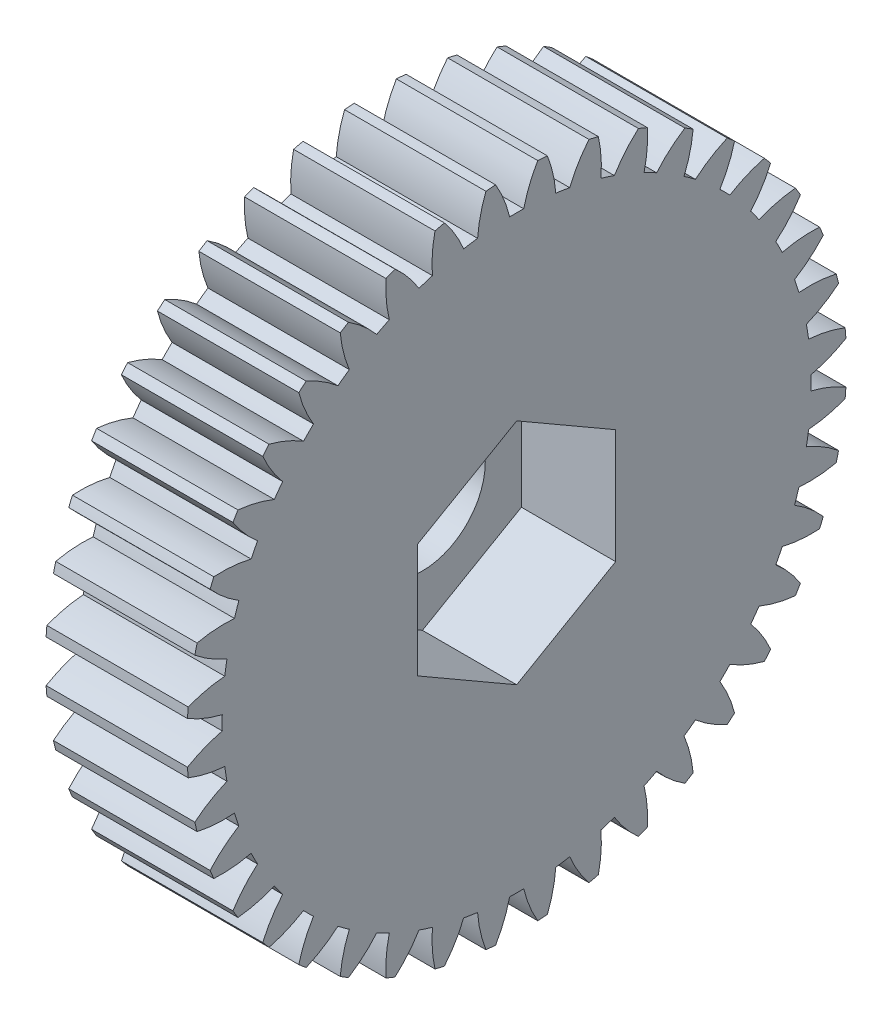
SolidWorks part; units mm, degrees
ref_plane "Plane1" through (0, 0, 0) normal (0, 0, 1) x (1, 0, 0)
ref_plane "Plane2" through (0, 0, 0) normal (0, 1, 0) x (1, 0, 0)
ref_plane "Plane3" through (0, 0, 0) normal (1, 0, 0) x (0, 0, -1)
sketch "HoldingSke" plane through (0, 0, 0) normal (0, 1, 0) x (1, 0, 0)
  line L0 (0, 0) -> (0.766, -0.6428)
  line L1 (-15, 0) -> (100, 0) construction
  line L2 (0, 0) -> (-2.1039, 2.3779)
  line L3 (0, 0) -> (-11.863, 4.5341)
  line L4 (0, 0) -> (6.6156, 5.5511)
  line L5 (0, 0) -> (-46.8476, -17.4728)
  line L6 (0, 0) -> (-7.4607, -5.0337)
  line L7 (-2.1039, 2.3779) -> (8.6586, 51.2059)
  line L8 (-76.2, 54.61) -> (-75.5, 54.61)
  line L9 (-71.009, 38.7566) -> (-53.1078, 45.2721)
  line L10 (-76.2, 71.12) -> (104.1128, 71.12)
  line L11 (0, 0) -> (-9, 0)
  line L12 (-76.2, 101.6) -> (-76.162, 101.6)
  line L13 (24.9733, 27.94) -> (52.9518, 28.4284)
  line L14 (24.9733, 27.94) -> (24.9743, 27.94)
  line L15 (24.9733, 27.94) -> (100.4006, 29.5858)
  line L16 (-63.627, -1) -> (-12.827, -1)
  circle A0 centre (0, 0) radius 2
  circle A1 centre (0, 0) radius 18.749
  circle A2 centre (0, 0) radius 37.5
  circle A3 centre (0, 0) radius 2
  dimension "MHD" = 37.498
  dimension "Hub_dia" = 75
  dimension "Bore" = 4
  dimension "MBD" = 4
  dimension "Num_teeth" = 40
  dimension "Pitch" = 1
  dimension "Overall_len" = 50
  dimension "Show_teeth" = 40
  dimension "Thickness" = 9
  dimension "OAL" = 50.0001
  dimension "T_dim" = 0.7
  dimension "Ap" = 20
  dimension "H" = 19.05
  dimension "Pitch_radius" = 180.3128
  dimension "Width" = 9
  dimension "Backlash" = 0.038
  dimension "Addendum_fac" = 1
  dimension "Dedendum_fac" = 1.25
  dimension "Clearance_fac" = 0.25
  dimension "Dedendum_add" = 0.001
  dimension "Module" = 1
sketch "BasProSke" plane through (0, 0, 0) normal (0, 1, 0) x (1, 0, 0)
  line L0 (-10, 0) -> (60, 0) construction
  line L1 (0, 0) -> (0, 21)
  line L2 (0, 0) -> (9, 0)
  line L3 (9, 0) -> (9, 21)
  line L4 (9, 21) -> (0, 21)
  dimension "Thickness" = 9
  dimension "Diameter" = 42
revolve "Base-Revolve" add sketch "BasProSke" angle 360 about L0
sketch "TooCutSke" plane through (0, 0, 0) normal (1, 0, 0) x (0, 0, -1)
  line L1 (0, 0) -> (0, 107) construction
  line L2 (0, 0) -> (-0.8517, 19.9819) construction
  line L3 (0, 0) -> (-3.1363, 39.8509) construction
  line L4 (-0.8517, 19.9819) -> (-1.5682, 19.9255) construction
  arc A0 (0.4487, 18.7436) -> (-0.4487, 18.7436) centre (0, 0) ccw
  arc A1 (1.3547, 20.9817) -> (-1.3547, 20.9817) centre (0, 0) ccw
  circle A2 centre (0, 0) radius 20 construction
  circle A3 centre (0, 0) radius 18.7939 construction
  arc A4 (-0.4487, 18.7436) -> (-1.3547, 20.9817) centre (-8.2322, 16.895) ccw
  arc A5 (1.3547, 20.9817) -> (0.4487, 18.7436) centre (8.2322, 16.895) ccw
  dimension "Root_dia" = 37.498
  dimension "Overcut_dia" = 42.0508
  dimension "Pitch_dia" = 40
  dimension "Base_dia" = 37.5877
  dimension "Flank_rad" = 8
  dimension "Half_ang" = 4.5
  dimension "Half_CT" = 0.7187
extrude "ToothCut" cut sketch "TooCutSke" along normal through all
fillet "Breaks" [suppressed] radius 0.02 tangent propagation no
fillet "RootFillets" [suppressed] radius 0.251
pattern_circular "TeethCuts" count 40 every 9 about axis through (-10, 0, 0) along (1, 0, 0) of "ToothCut", "RootFillets", "Breaks"
sketch "HubNeaOneSke" plane through (0, 0, 0) normal (-1, 0, 0) x (0, 0, 1)
  circle A0 centre (0, 0) radius 18.749
  dimension "Diameter" = 37.498
extrude "HubNearOne" [suppressed] add sketch "HubNeaOneSke" along normal blind 41.0001
sketch "HubNeaBotSke" plane through (0, 0, 0) normal (-1, 0, 0) x (0, 0, 1)
  circle A0 centre (0, 0) radius 18.749
  dimension "Diameter" = 37.498
extrude "HubNearBoth" [suppressed] add sketch "HubNeaBotSke" along normal blind 20.5
ref_plane "FarPln" through (9, 0, 0) normal (1, 0, 0) x (0, 0, -1)
sketch "HubFarSke" plane through (9, 0, 0) normal (1, 0, 0) x (0, 0, -1)
  circle A0 centre (0, 0) radius 18.749
  dimension "Diameter" = 37.498
extrude "HubFar" [suppressed] add sketch "HubFarSke" along normal blind 20.5
sketch "BorSke" plane through (0, 0, 0) normal (1, 0, 0) x (0, 0, -1)
  circle A0 centre (0, 0) radius 2
extrude "Bore" cut sketch "BorSke" along normal mid plane 100.0001
sketch "KeySke" plane through (0, 0, 0) normal (1, 0, 0) x (0, 0, -1)
  line L0 (-0.8, 0) -> (-0.8, 2.7)
  line L1 (-0.8, 2.7) -> (0.8, 2.7)
  line L2 (0.8, 2.7) -> (0.8, 0)
  line L3 (0, 0) -> (0, 34) construction
  line L4 (-0.8, 0) -> (0.8, 0)
  dimension "Offset" = 2.7
  dimension "Width" = 1.6
extrude "Keyway" [suppressed] cut sketch "KeySke" along normal mid plane 100.0001
pattern_circular "Keyway2" [suppressed] count 2 every 90 about axis through (-10, 0, 0) along (1, 0, 0)
sketch "Sketch1" plane through (9, 0, 0) normal (1, 0, 0) x (0, 0, -1)
  line L1 (0, 7.2746) -> (-6.3, 3.6373)
  line L2 (-6.3, 3.6373) -> (-6.3, -3.6373)
  line L3 (-6.3, -3.6373) -> (0, -7.2746)
  line L4 (0, -7.2746) -> (6.3, -3.6373)
  line L5 (6.3, -3.6373) -> (6.3, 3.6373)
  line L6 (6.3, 3.6373) -> (0, 7.2746)
  circle A0 centre (0, 0) radius 7.2746
  circle A2 centre (0, 0) radius 6.3 construction
  circle A3 centre (0, 0) radius 4
  dimension "D1" = 8
  dimension "D2" = 12.6
extrude "Cut-Extrude1" cut sketch "Sketch1" against normal blind 6 contours L1 L2 L3 L4 L5 L6
extrude "Cut-Extrude2" cut sketch "Sketch1<7>" against normal through all contours A3 region at (9, 0, 0)
sketch "Sketch1<7>" plane through (9, 0, 0) normal (1, 0, 0) x (0, 0, -1) same geometry as "Sketch1"
sketch "Sketch2" plane through (0, 0, 0) normal (-1, 0, 0) x (0, 0, 1)
  circle A0 centre (0, 0) radius 6.5
  circle A1 centre (0, 0) radius 4
  dimension "D1" = 13
  dimension "D2" = 8
extrude "Boss-Extrude1" add sketch "Sketch2" along normal blind 1.8
sketch "Sketch3" plane through (3, 0, 0) normal (1, 0, 0) x (0, 0, -1)
  line L1 (4, 4) -> (-4, 4)
  line L2 (4, 4) -> (4, -4)
  line L3 (4, -4) -> (-4, -4)
  line L4 (-4, 4) -> (-4, -4)
  line L6 (5.5, 5.5) -> (5.5, -5.5)
  line L7 (5.5, -5.5) -> (-5.5, -5.5)
  line L8 (-5.5, 5.5) -> (-5.5, -5.5)
  line L9 (5.5, 5.5) -> (-5.5, 5.5)
  line L10 (5.5, 4) -> (5.6718, 4)
  line L11 (6.3, 3.6373) -> (0, 7.2746) construction
  line L12 (5.5, -4) -> (5.6718, -4)
  line L13 (0, -7.2746) -> (6.3, -3.6373) construction
  line L14 (-5.5, -4) -> (-5.6718, -4)
  line L15 (-6.3, -3.6373) -> (0, -7.2746) construction
  line L16 (-5.5, 4) -> (-5.6718, 4)
  line L17 (0, 7.2746) -> (-6.3, 3.6373) construction
  circle A0 centre (0, 0) radius 4 construction
  line M10 (6.3, 3.6373) -> (0, 7.2746)
  line M11 (0, 7.2746) -> (-6.3, 3.6373)
  line M13 (-6.3, -3.6373) -> (0, -7.2746)
  line M14 (0, -7.2746) -> (6.3, -3.6373)
  dimension "D1" = 1.5
extrude "Boss-Extrude2" [suppressed] add sketch "Sketch3" along normal blind 0.3 contours L9 L8 L7 L6 L4 L1 L2 L3 M10 M11 M13 M14 | L12 L6 M14 | L6 L10 M10 | L16 L8 M11 | L8 L14 M13
equation "' \"Module@HoldingSke\" = 6.35"
equation "' \"Num_teeth@HoldingSke\" = 12"
equation "' \"Ap@HoldingSke\" =  20"
equation "' \"Ap@HoldingSke\" = 20"
equation "' \"Width@HoldingSke\" = 0.5 * 25.4"
equation "' \"Hub_dia@HoldingSke\"= 1 * 25.4"
equation "' \"Hub_dia@HoldingSke\" = 1 * 25.4"
equation "' \"Overall_len@HoldingSke\" = 1.0 * 25.4"
equation "' \"Bore@HoldingSke\" = 0.75 * 25.4"
equation "' \"T_dim@HoldingSke\" = 0.1 * 25.4"
equation "' \"Width@KeySke\" = 0.25 * 25.4"
equation "' \"Show_teeth@HoldingSke\" = 13"
equation "' \"Backlash@HoldingSke\" = 0.009 * 25.4"
equation "' \"Addendum_fac@HoldingSke\" = 1.0"
equation "' \"Dedendum_fac@HoldingSke\" = 1.25"
equation "' \"Dedendum_add@HoldingSke\" = 0.00005 * 25.4"
equation "' \"Clearance_fac@HoldingSke\" = 0.25"
equation "\"Pitch@HoldingSke\" = 1 / \"Module@HoldingSke\""
equation "\"Overcut_dia@TooCutSke\" = (\"Num_teeth@HoldingSke\" + 2 * \"Addendum_fac@HoldingSke\") / \"Pitch@HoldingSke\" + 0.002 * 25.4"
equation "\"Pitch_dia@TooCutSke\" = \"Num_teeth@HoldingSke\" / \"Pitch@HoldingSke\""
equation "\"Base_dia@TooCutSke\" = \"Num_teeth@HoldingSke\" / \"Pitch@HoldingSke\" * cos((\"Ap@HoldingSke\"  * 3.14159265 / 180))"
equation "\"Root_dia@TooCutSke\" = (\"Num_teeth@HoldingSke\" + 2) / \"Pitch@HoldingSke\" - 2 * (\"Addendum_fac@HoldingSke\" + \"Dedendum_fac@HoldingSke\") / \"Pitch@HoldingSke\" - \"Dedendum_add@HoldingSke\" * 2"
equation "\"Half_ang@TooCutSke\" = 180 / \"Num_teeth@HoldingSke\""
equation "\"Half_CT@TooCutSke\" = \"Num_teeth@HoldingSke\" / \"Pitch@HoldingSke\" * sin((3.14159265 / 2 / \"Num_teeth@HoldingSke\")) / 2 - 7 * \"Backlash@HoldingSke\" / 4"
equation "\"Flank_rad@TooCutSke\" = \"Num_teeth@HoldingSke\" / \"Pitch@HoldingSke\" / 5"
equation "\"Radius@RootFillets\" = \"Clearance_fac@HoldingSke\" / \"Pitch@HoldingSke\" + \"Dedendum_add@HoldingSke\""
equation "\"Break_rad@Breaks\" = 0.02 / \"Pitch@HoldingSke\""
equation "\"Thickness@HoldingSke\" = \"Width@HoldingSke\""
equation "\"OAL@HoldingSke\" = \"Thickness@HoldingSke\""
equation "\"MHD@HoldingSke\" = (\"Num_teeth@HoldingSke\" + 2) / \"Pitch@HoldingSke\" - 2 * (\"Addendum_fac@HoldingSke\" + \"Dedendum_fac@HoldingSke\")  / \"Pitch@HoldingSke\" - \"Dedendum_add@HoldingSke\" * 2"
equation "\"MBD@HoldingSke\" = (\"Num_teeth@HoldingSke\" + 2) / \"Pitch@HoldingSke\" - 2 * (\"Addendum_fac@HoldingSke\" + \"Dedendum_fac@HoldingSke\")  / \"Pitch@HoldingSke\" - \"Dedendum_add@HoldingSke\" * 2 - 0.002 * 25.4"
equation "\"MHD@HoldingSke\" = ((sgn( \"MHD@HoldingSke\" - \"Hub_dia@HoldingSke\" )-1)*( \"MHD@HoldingSke\" - \"Hub_dia@HoldingSke\" ))/-2+ \"Hub_dia@HoldingSke\""
equation "\"MBD@HoldingSke\" = ((sgn( \"MBD@HoldingSke\" - \"Bore@HoldingSke\" )-1)*( \"MBD@HoldingSke\" - \"Bore@HoldingSke\" ))/-2+ \"Bore@HoldingSke\""
equation "\"OAL@HoldingSke\" = ((sgn( \"OAL@HoldingSke\" - \"Overall_len@HoldingSke\" )+1)*( \"OAL@HoldingSke\" - \"Overall_len@HoldingSke\" ))/2 + \"Overall_len@HoldingSke\" + 0.000002 * 25.4"
equation "\"Num_teeth@TeethCuts\" = int( \"Show_teeth@HoldingSke\" ) + 1"
equation "\"Num_teeth@TeethCuts\" = ((sgn( \"Num_teeth@TeethCuts\" - \"Num_teeth@HoldingSke\" )-1)*( \"Num_teeth@TeethCuts\" - \"Num_teeth@HoldingSke\" ))/-2+ \"Num_teeth@HoldingSke\""
equation "\"Num_teeth@TeethCuts\" = ((sgn( \"Num_teeth@TeethCuts\" - 2.0)+1)*( \"Num_teeth@TeethCuts\" - 2.0))/2 +2.0"
equation "\"Angle@TeethCuts\" = 360.0 / \"Num_teeth@HoldingSke\""
equation "\"Diameter@BasProSke\" = (\"Num_teeth@HoldingSke\" + 2 * \"Addendum_fac@HoldingSke\") / \"Pitch@HoldingSke\""
equation "\"Thickness@BasProSke\"  = \"Thickness@HoldingSke\""
equation "' \"Fillet_rad@BasProSke\" =  \"Thickness@HoldingSke\" * 0.05"
equation "' \"Fillet_rad@BasProSke\" = \"Thickness@HoldingSke\" * 0.05"
equation "\"MHD@HoldingSke\" = ((sgn( \"MHD@HoldingSke\" - \"Root_dia@TooCutSke\" )-1)*( \"MHD@HoldingSke\" - \"Root_dia@TooCutSke\" ))/-2+ \"Root_dia@TooCutSke\""
equation "\"Diameter@HubNeaOneSke\" = \"MHD@HoldingSke\""
equation "\"Length@HubNearOne\" = \"OAL@HoldingSke\" - \"Thickness@BasProSke\""
equation "\"Diameter@HubNeaBotSke\" = \"MHD@HoldingSke\""
equation "\"Length@HubNearBoth\" = ( \"OAL@HoldingSke\" - \"Thickness@BasProSke\" ) / 2.0"
equation "\"Thickness@FarPln\" = \"Thickness@BasProSke\""
equation "\"Diameter@HubFarSke\" = \"MHD@HoldingSke\""
equation "\"Length@HubFar\" = ( \"OAL@HoldingSke\" - \"Thickness@BasProSke\" ) / 2.0"
equation "\"Diameter@BorSke\" = \"MBD@HoldingSke\""
equation "\"D1@Bore\" = \"OAL@HoldingSke\" * 2.0"
equation "\"D1@Keyway\" = \"OAL@HoldingSke\" * 2.0"
equation "\"Offset@KeySke\" = \"T_dim@HoldingSke\" + \"MBD@HoldingSke\" / 2.0"
